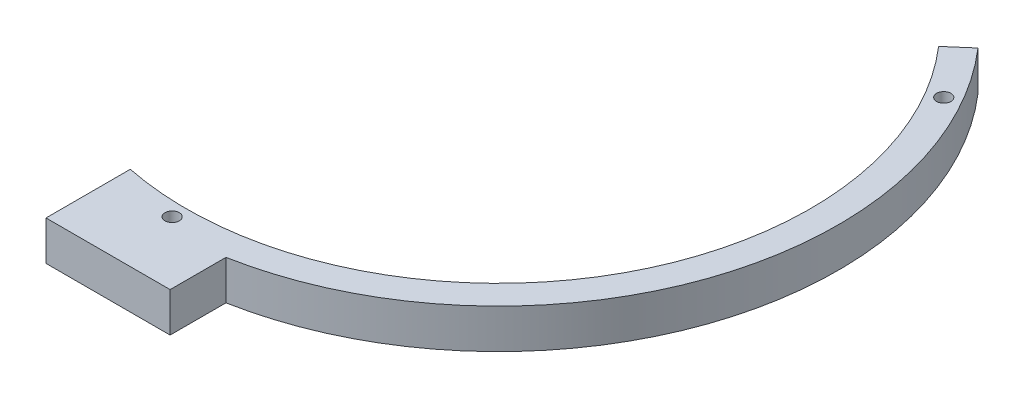
SolidWorks part; units mm, degrees
ref_plane "Front Plane" through (0, 0, 0) normal (0, 0, 1) x (1, 0, 0)
ref_plane "Top Plane" through (0, 0, 0) normal (0, 1, 0) x (1, 0, 0)
ref_plane "Right Plane" through (0, 0, 0) normal (1, 0, 0) x (0, 0, -1)
sketch "Sketch1" plane through (0, 0, 0) normal (0, 1, 0) x (1, 0, 0)
  line L0 (-10, -53.8799) -> (-10, -62.8799)
  line L1 (-10, -62.8799) -> (10, -62.8799)
  line L2 (10, -62.8799) -> (10, -53.8799)
  arc A0 (10, -53.8799) -> (-10, -53.8799) centre (0, 0) ccw
  circle A1 centre (0, 0) radius 50.3
  point P1 (-9.9963, -49.301)
  point P9 (0, -62.8799)
  dimension "D1" = 4.5
  dimension "D2" = 109.6
  dimension "D3" = 20
  dimension "D4" = 9
extrude "Boss-Extrude1" add sketch "Sketch1" along normal blind 6.35
sketch "Sketch2" plane through (0, 6.35, 0) normal (0, 1, 0) x (1, 0, 0)
  line L0 (0, -50.3) -> (0, -54.8) construction
  circle A0 centre (0, 0) radius 50.3 construction
  circle A1 centre (0, 0) radius 54.8 construction
  circle A2 centre (0, -52.55) radius 1.15
  dimension "D1" = 2.3
extrude "Cut-Extrude1" cut sketch "Sketch2" against normal up to next
pattern_circular "CirPattern1" count 3 over 360 about axis through (0, 6.35, 0) along (0, 1, 0) of "Cut-Extrude1"
sketch "Sketch3" plane through (0, 6.35, 0) normal (0, 1, 0) x (1, 0, 0)
  line L0 (-10, -53.8799) -> (-10, -49.2959)
  line L1 (41.3769, 35.9304) -> (37.9792, 32.9799)
  line L2 (0, 0) -> (41.3769, 35.9304) construction
  circle A0 centre (0, 0) radius 50.3 construction
  arc A1 (10, -53.8799) -> (-10, -53.8799) centre (0, 0) ccw construction
  circle A2 centre (0, 0) radius 54.8
  circle A3 centre (45.5096, 26.275) radius 1.15 construction
  circle A4 centre (0, 0) radius 50.3
  circle M5 centre (-45.5096, 26.275) radius 1.15
  arc M7 (10, -53.8799) -> (-10, -53.8799) centre (0, 0) ccw
  circle M11 centre (0, 0) radius 50.3
  dimension "D1" = 10
extrude "Cut-Extrude2" cut sketch "Sketch3" against normal up to next contours L1 L0 M7 M11 M5 region at (-47.4408, 6.35, -27.139)
